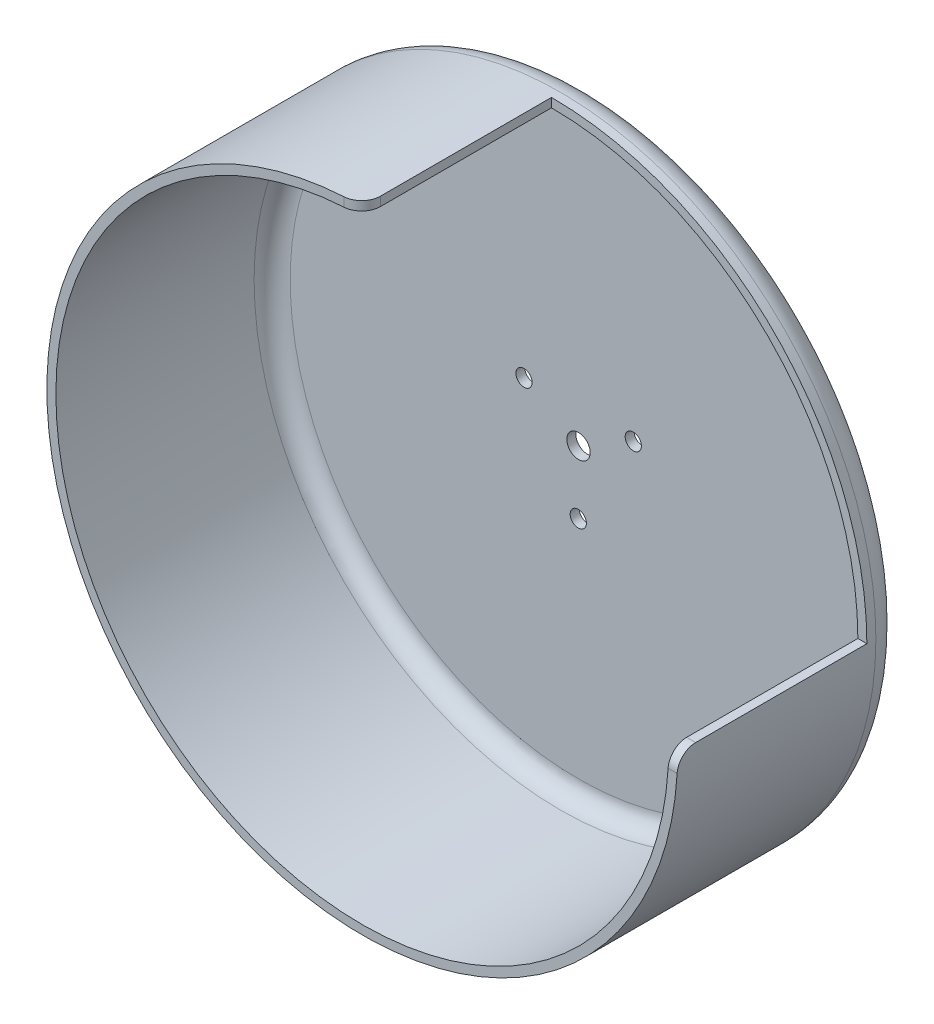
SolidWorks part; units mm, degrees
material "橡胶"
ref_plane "前视基准面" through (0, 0, 0) normal (0, 0, 1) x (1, 0, 0)
ref_plane "上视基准面" through (0, 0, 0) normal (0, 1, 0) x (1, 0, 0)
ref_plane "右视基准面" through (0, 0, 0) normal (1, 0, 0) x (0, 0, -1)
sketch "草图1" plane through (0, 0, 0) normal (0, 0, 1) x (1, 0, 0)
  circle A0 centre (0, 0) radius 175
  dimension "D1" = 350
extrude "凸台-拉伸1" add sketch "草图1" along normal blind 125
shell "抽壳3" thickness 5 removed face at (175, 0, 125)
sketch "草图2" plane through (0, 0, 0) normal (0, 1, 0) x (1, 0, 0)
  line L0 (175, 0) -> (-175, 0) construction
  line L1 (175, -125) -> (170, -125)
  line L2 (175, -125) -> (175, -20)
  line L3 (175, -20) -> (170, -20)
  line L4 (170, -125) -> (170, -20)
  line L5 (0, 0) -> (0, -125) construction
  line L6 (-175, -125) -> (175, -125) construction
  dimension "D1" = 5
  dimension "D2" = 20
revolve "切除-旋转1" cut sketch "草图2" angle 90 about L5
fillet "圆角1" radius 10 1 edges at (170, 0, 5)
fillet "圆角2" radius 15 1 edges at (175, 0, 0)
sketch "草图3" plane through (0, 0, 5) normal (0, 0, 1) x (1, 0, 0)
  circle A0 centre (0, 0) radius 6.5
  dimension "D1" = 13
extrude "切除-拉伸1" cut sketch "草图3" against normal blind 125
fillet "圆角3" radius 10 1 edges at (0, 172.5, 125)
fillet "圆角4" radius 10 1 edges at (172.5, 0, 125)
sketch "草图4" plane through (0, 0, 5) normal (0, 0, 1) x (1, 0, 0)
  line L1 (0, 0) -> (-121.203, 69.9766) construction
  line L2 (0, 0) -> (-119.085, 0) construction
  dimension "D1" = 30
sketch "草图5" plane through (0, 0, 5) normal (0, 0, 1) x (1, 0, 0)
  circle A0 centre (-30.2436, 17.6161) radius 4.5
  dimension "D1" = 9
  dimension "D2" = 35
extrude "切除-拉伸2" cut sketch "草图5" against normal blind 125
pattern_circular "阵列(圆周)1" count 3 over 360 about axis through (0, 0, -120) along (0, 0, 1) of "切除-拉伸2"
